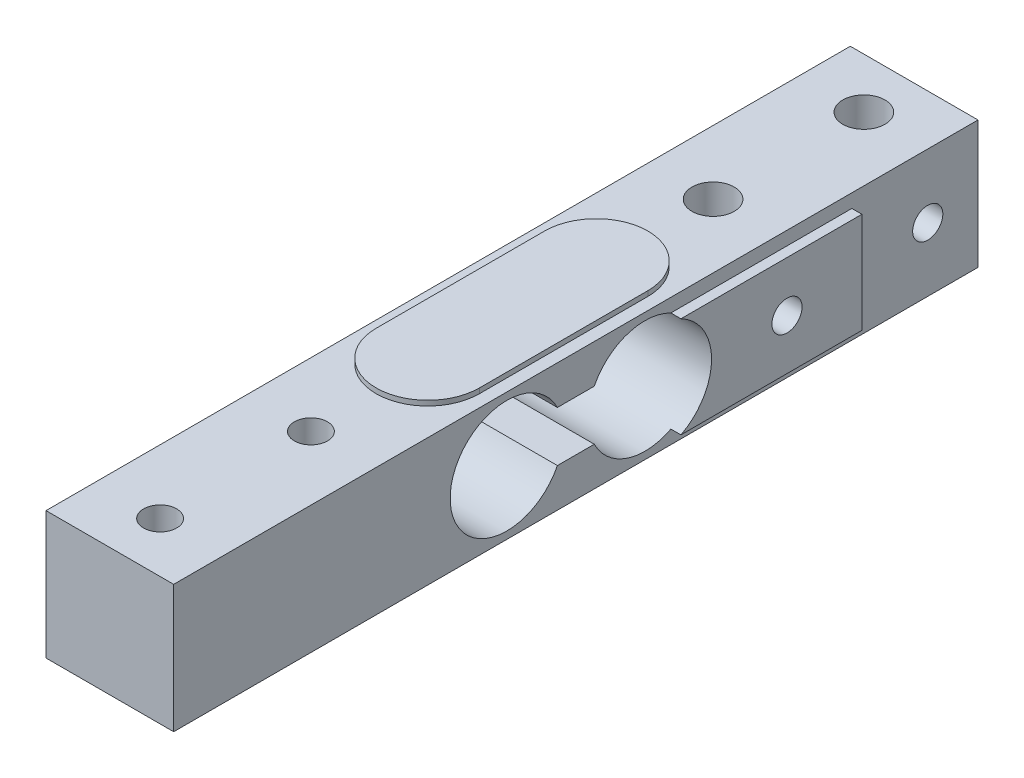
SolidWorks part; units mm, degrees
ref_plane "Front Plane" through (0, 0, 0) normal (0, 0, 1) x (1, 0, 0)
ref_plane "Top Plane" through (0, 0, 0) normal (0, 1, 0) x (1, 0, 0)
ref_plane "Right Plane" through (0, 0, 0) normal (1, 0, 0) x (0, 0, -1)
sketch "Sketch1" plane through (0, 0, 0) normal (1, 0, 0) x (0, 0, -1)
  line L1 (-40, -6.35) -> (40, -6.35)
  line L2 (-40, -6.35) -> (-40, 6.35)
  line L3 (-40, 6.35) -> (40, 6.35)
  line L4 (40, -6.35) -> (40, 6.35)
  line L5 (-40, -6.35) -> (40, 6.35) construction
  line L6 (-40, 6.35) -> (40, -6.35) construction
  point P0 (0, 0)
  dimension "D1" = 12.7
  dimension "D2" = 80
extrude "Boss-Extrude1" add sketch "Sketch1" along normal mid plane 12.7
sketch "Sketch2" plane through (0, 0, 0) normal (1, 0, 0) x (0, 0, -1)
  line L0 (-6.875, 0) -> (6.875, 0) construction
  line L1 (-12.5, 0) -> (12.5, 0) construction
  circle A0 centre (-6.875, 0) radius 5.625
  circle A1 centre (6.875, 0) radius 5.625
  point P4 (0, 0)
  dimension "D2" = 11.25
  dimension "D1" = 25
extrude "Cut-Extrude1" cut sketch "Sketch2" against normal through all both and the other way through all
sketch "Sketch3" plane through (0, 0, 0) normal (1, 0, 0) x (0, 0, -1)
  line L1 (-11.9139, -2.5) -> (11.9139, -2.5)
  line L2 (-11.9139, -2.5) -> (-11.9139, 2.5)
  line L3 (-11.9139, 2.5) -> (11.9139, 2.5)
  line L4 (11.9139, -2.5) -> (11.9139, 2.5)
  line L5 (-11.9139, -2.5) -> (11.9139, 2.5) construction
  line L6 (-11.9139, 2.5) -> (11.9139, -2.5) construction
  circle A0 centre (6.875, 0) radius 5.625 construction
  point P0 (0, 0)
  dimension "D1" = 5
extrude "Cut-Extrude2" cut sketch "Sketch3" against normal through all both and the other way through all
hole_wizard "M4x0.7 Tapped Hole1" positions "Sketch18" profile "Sketch5" tap size "M4x0.7" standard "ANSI Metric" end condition through all
sketch "Sketch18" plane through (0, 6.35, 0) normal (0, 1, 0) x (1, 0, 0)
  line L0 (0, 35) -> (0, 20) construction
  line L2 (0, 20) -> (0, -20) construction
  line L4 (0, -20) -> (0, -35) construction
  point P0 (0, 35)
  point P2 (0, 20)
  point P4 (0, -20)
  point P6 (0, -35)
  point P20 (0, 0)
  dimension "D1" = 40
  dimension "D2" = 15
cosmetic thread "Hole Thread1"
cosmetic thread "Hole Thread2"
sketch "Sketch5" plane through (0, 6.35, -35) normal (1, 0, 0) x (0, 0, 1)
  line L0 (0, 0) -> (0, 12.7)
  line L1 (0, 12.7) -> (1.65, 12.7)
  line L2 (1.65, 12.7) -> (1.65, 0)
  line L5 (1.65, 0) -> (0, 0)
  line L11 (0, -6.35) -> (0, 107.95) construction
  dimension "Thru Tap Drill Dia." = 3.3
  dimension "Thru Tap Drill Depth" = 12.7
cosmetic thread "Hole Thread7"
cosmetic thread "Hole Thread8"
sketch "Sketch8" plane through (0, 6.35, 0) normal (0, 1, 0) x (1, 0, 0)
  line L0 (0, -8.3778) -> (0, 8.3778) construction
  line L1 (-5.1373, -8.3778) -> (-5.1373, 8.3778)
  line L2 (5.1373, -8.3778) -> (5.1373, 8.3778)
  arc A0 (-5.1373, -8.3778) -> (5.1373, -8.3778) centre (0, -8.3778) ccw
  arc A1 (5.1373, 8.3778) -> (-5.1373, 8.3778) centre (0, 8.3778) ccw
  point P2 (0, 0)
extrude "Goo" add sketch "Sketch8" along normal mid plane 1
mirror "Mirror1" about plane through (0, 0, 0) normal (0, 1, 0) of "Goo"
ref_axis "Axis1" through (0, -6.35, -20) along (0, 1, 0)
ref_axis "Axis2" through (0, -6.35, -35) along (0, 1, 0)
sketch "Sketch9" plane through (6.35, 0, 0) normal (1, 0, 0) x (0, 0, -1)
  line L1 (9.4519, -5) -> (27.4519, -5)
  line L3 (9.4519, 5) -> (27.4519, 5)
  line L4 (27.4519, -5) -> (27.4519, 5)
  line L5 (9.4519, -5) -> (27.4519, 5) construction
  line L6 (9.4519, 5) -> (27.4519, -5) construction
  arc A0 (1.8361, -2.5) -> (1.8361, 2.5) centre (6.875, 0) ccw construction
  arc A1 (9.4519, -5) -> (9.4519, 5) centre (6.875, 0) ccw
  point P0 (18.4519, 0)
  point P5 (0, 0)
  point P9 (0, 0)
  point P11 (8.3165, 5.4372)
  point P12 (28.5366, -4.2701)
  point P13 (27.7335, 4.8445)
  dimension "D1" = 18
  dimension "D2" = 10
extrude "Boss-Extrude5" add sketch "Sketch9" along normal mid plane 2
hole_wizard "Ø3.0mm Dowel Hole1" positions "Sketch14" profile "Sketch12" hole size "Ø3.0" standard "ANSI Metric" end condition through all
sketch "Sketch14" plane through (-6.35, 0, 0) normal (-1, 0, 0) x (0, 0, 1)
  line L0 (-20, -6.35) -> (-20, 6.35) construction
  line L1 (-35, -6.35) -> (-35, 6.35) construction
  point P0 (-20, 0)
  point P2 (-35, 0)
  point P12 (-23.9334, 0)
  point P15 (0, 0)
  point P16 (0, 0)
sketch "Sketch12" plane through (-6.35, 0, -20) normal (0, 1, 0) x (0, 0, 1)
  line L0 (0, 0) -> (0, 13.7)
  line L1 (0, 13.7) -> (1.5, 13.7)
  line L2 (1.5, 13.7) -> (1.5, 0)
  line L5 (1.5, 0) -> (0, 0)
  line L11 (0, -6.35) -> (0, 107.95) construction
  dimension "Thru Hole Dia." = 3
  dimension "Thru Hole Depth" = 13.7
hole_wizard "M5x0.8 Tapped Hole1" positions "Sketch17" profile "Sketch16" tap size "M5x0.8" standard "ANSI Metric" end condition through all
sketch "Sketch17" plane through (0, 6.35, 0) normal (0, 1, 0) x (1, 0, 0)
  point P0 (0, 35)
  point P3 (0, 20)
sketch "Sketch16" plane through (0, 6.35, -35) normal (1, 0, 0) x (0, 0, 1)
  line L0 (0, 0) -> (0, 13.2)
  line L1 (0, 13.2) -> (2.1, 13.2)
  line L2 (2.1, 13.2) -> (2.1, 0)
  line L5 (2.1, 0) -> (0, 0)
  line L11 (0, -6.35) -> (0, 107.95) construction
  dimension "Thru Tap Drill Dia." = 4.2
  dimension "Thru Tap Drill Depth" = 13.2
cosmetic thread "Hole Thread5"
cosmetic thread "Hole Thread6"
